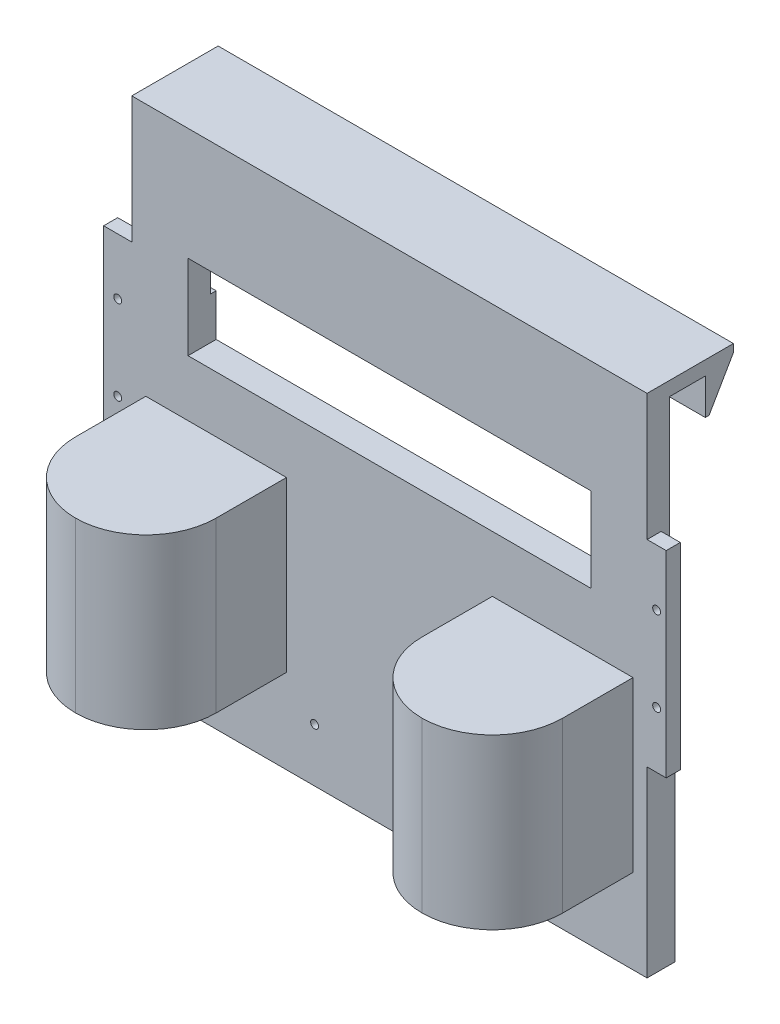
SolidWorks part; units mm, degrees
ref_plane "Alzado" through (0, 0, 0) normal (0, 0, 1) x (1, 0, 0)
ref_plane "Planta" through (0, 0, 0) normal (0, 1, 0) x (1, 0, 0)
ref_plane "Vista lateral" through (0, 0, 0) normal (1, 0, 0) x (0, 0, -1)
sketch "Croquis1" plane through (0, 0, 0) normal (0, 0, 1) x (1, 0, 0)
  line L1 (0, 0) -> (180, 0)
  line L2 (0, 0) -> (0, 180)
  line L3 (0, 180) -> (180, 180)
  line L4 (180, 0) -> (180, 180)
  dimension "D1" = 180
extrude "Saliente-Extruir1" add sketch "Croquis1" along normal blind 30.7
sketch "Croquis2" plane through (0, 0, 0) normal (0, 0, -1) x (-1, 0, 0)
  line L0 (-180, 0) -> (-180, 180) construction
  line L1 (-180, 162.21) -> (0, 162.21)
  line L2 (-180, 162.21) -> (-180, 0)
  line L3 (-180, 0) -> (0, 0)
  line L4 (0, 162.21) -> (0, 0)
  line L5 (-180, 180) -> (0, 180) construction
  dimension "D1" = 17.79
extrude "Cortar-Extruir1" cut sketch "Croquis2" against normal blind 20.7
sketch "Croquis3" plane through (0, 0, 0) normal (-1, 0, 0) x (0, 0, 1)
  line L0 (30.7, 180) -> (0, 180) construction
  line L1 (20.7, 162.21) -> (10, 162.21)
  line L2 (20.7, 162.21) -> (20.7, 175)
  line L3 (20.7, 175) -> (10, 175)
  line L4 (10, 162.21) -> (10, 175)
  dimension "D1" = 5
  dimension "D2" = 10.7
extrude "Cortar-Extruir2" cut sketch "Croquis3" against normal blind 274.7
sketch "Croquis4" plane through (180, 0, 0) normal (1, 0, 0) x (0, 0, -1)
  line L8 (-20.7, 0) -> (-20.7, 175)
  line L9 (-20.7, 175) -> (-10, 175)
  line L10 (-10, 175) -> (-10, 162.21)
  line L11 (-10, 162.21) -> (0, 162.21)
  line L12 (0, 162.21) -> (0, 180)
  line L13 (0, 180) -> (-30.7, 180)
  line L14 (-30.7, 180) -> (-30.7, 0)
  line L15 (-30.7, 0) -> (-20.7, 0)
  line L16 (-20.7, 0) -> (-20.7, 175)
  line L17 (-20.7, 175) -> (-10, 175)
  line L18 (-10, 175) -> (-10, 162.21)
  line L19 (-10, 162.21) -> (0, 162.21)
  line L20 (0, 162.21) -> (0, 180)
  line L21 (0, 180) -> (-30.7, 180)
  line L22 (-30.7, 180) -> (-30.7, 0)
  line L23 (-30.7, 0) -> (-20.7, 0)
  dimension "D1" = 0
extrude "Saliente-Extruir2" add sketch "Croquis4" along normal blind 20
sketch "Croquis5" plane through (0, 0, 20.7) normal (0, 0, -1) x (-1, 0, 0)
  line L0 (-10, 125) -> (-10, 0) construction
  line L1 (-55, 38) -> (-10, 38)
  line L2 (-55, 38) -> (-55, 0)
  line L3 (-55, 0) -> (0, 0)
  line L4 (0, 38) -> (0, 0)
  line L5 (-148.2, 38) -> (-193.2, 38)
  line L6 (-148.2, 38) -> (-148.2, 0)
  line L7 (-148.2, 0) -> (-200, 0)
  line L8 (-200, 38) -> (-200, 0)
  line L9 (0, 180) -> (-10, 180)
  line L10 (0, 180) -> (0, 135)
  line L11 (0, 135) -> (-10, 135)
  line L12 (-10, 180) -> (-10, 135)
  line L13 (-193.2, 0) -> (-193.2, 125) construction
  line L14 (-200, 180) -> (-193.2, 180)
  line L15 (-200, 180) -> (-200, 135)
  line L16 (-200, 135) -> (-193.2, 135)
  line L17 (-193.2, 180) -> (-193.2, 135)
  line L20 (-200, 38) -> (-200, 65)
  line L21 (-200, 65) -> (-193.2, 65)
  line L22 (-193.2, 38) -> (-193.2, 65)
  line L24 (0, 38) -> (0, 65)
  line L25 (0, 65) -> (-10, 65)
  line L26 (-10, 38) -> (-10, 65)
  dimension "D1" = 65
  dimension "D2" = 65
  dimension "D3" = 45
  dimension "D4" = 45
extrude "Cortar-Extruir3" cut sketch "Croquis5" along normal blind 147 and the other way blind 147
sketch "Croquis6" plane through (0, 0, 20.7) normal (0, 0, -1) x (-1, 0, 0)
  line L1 (-55, 0) -> (-148.2, 0)
  line L2 (-55, 0) -> (-55, 38)
  line L3 (-55, 38) -> (-148.2, 38)
  line L4 (-148.2, 0) -> (-148.2, 38)
  line L5 (-193.2, 65) -> (-200, 65)
  line L6 (-193.2, 65) -> (-193.2, 135)
  line L7 (-193.2, 135) -> (-200, 135)
  line L8 (-200, 65) -> (-200, 135)
  line L9 (0, 135) -> (-10, 135)
  line L10 (0, 135) -> (0, 65)
  line L11 (0, 65) -> (-10, 65)
  line L12 (-10, 135) -> (-10, 65)
extrude "Cortar-Extruir4" cut sketch "Croquis6" against normal blind 5
sketch "Croquis7" plane through (0, 0, 20.7) normal (0, 0, -1) x (-1, 0, 0)
  line L0 (-10, 175) -> (-10, 38) construction
  line L1 (-193.2, 175) -> (-10, 175)
  line L2 (-193.2, 175) -> (-193.2, 125)
  line L3 (-193.2, 125) -> (-10, 125)
  line L4 (-10, 175) -> (-10, 125)
  dimension "D1" = 50
extrude "Cortar-Extruir5" cut sketch "Croquis7" against normal blind 2
sketch "Croquis8" plane through (0, 38, 0) normal (0, -1, 0) x (1, 0, 0)
  line L1 (55, 30.7) -> (10, 30.7)
  line L2 (55, 30.7) -> (55, 20.7)
  line L3 (55, 20.7) -> (10, 20.7)
  line L4 (10, 30.7) -> (10, 20.7)
  line L5 (148.2, 30.7) -> (193.2, 30.7)
  line L6 (148.2, 30.7) -> (148.2, 20.7)
  line L7 (148.2, 20.7) -> (193.2, 20.7)
  line L8 (193.2, 30.7) -> (193.2, 20.7)
extrude "Saliente-Extruir3" add sketch "Croquis8" along normal up to surface (38 mm away) up to face at (101.6, 0, 28.2)
sketch "Croquis9" plane through (0, 0, 30.7) normal (0, 0, 1) x (1, 0, 0)
  line L0 (193.2, 180) -> (10, 180) construction
  line L1 (30, 140) -> (173.2, 140)
  line L2 (30, 140) -> (30, 110)
  line L3 (30, 110) -> (173.2, 110)
  line L4 (173.2, 140) -> (173.2, 110)
  line L5 (193.2, 135) -> (193.2, 180) construction
  line L6 (10, 180) -> (10, 135) construction
  line L7 (148.2, 0) -> (148.2, 38) construction
  line L8 (55, 0) -> (55, 38) construction
  line L10 (200, 65) -> (193.2, 65) construction
  line L11 (0, 135) -> (10, 135) construction
  line L12 (10, 65) -> (0, 65) construction
  line L13 (193.2, 135) -> (200, 135) construction
  circle A0 centre (5, 115) radius 1.4
  circle A1 centre (5, 85) radius 1.4
  circle A2 centre (196.6, 115) radius 1.4
  circle A3 centre (196.6, 85) radius 1.4
  circle A4 centre (128.2, 19) radius 1.4
  circle A5 centre (75, 19) radius 1.4
  point P26 (0, 0)
  point P27 (55, 19)
  point P28 (0, 0)
  point P31 (196.6, 65)
  point P32 (0, 0)
  point P35 (5, 135)
  dimension "D7" = 2.8
  dimension "D1" = 30
  dimension "D2" = 40
  dimension "D3" = 20
  dimension "D4" = 20
  dimension "D5" = 20
  dimension "D6" = 20
  dimension "D8" = 20
  dimension "D9" = 20
  dimension "D10" = 20
  dimension "D11" = 20
extrude "Cortar-Extruir6" cut sketch "Croquis9" against normal blind 20
chamfer "Chaflán1" distance 15 angle 30 1 edges at (101.6, 162.21, 0) first distance on face at (101.6, 171.105, 0)
sketch "Croquis10" plane through (0, 0, 30.7) normal (0, 0, 1) x (1, 0, 0)
  line L0 (10, 0) -> (193.2, 0) construction
  line L1 (138.2, 90) -> (188.2, 90)
  line L2 (138.2, 90) -> (138.2, 30)
  line L3 (138.2, 30) -> (188.2, 30)
  line L4 (188.2, 90) -> (188.2, 30)
  line L5 (15, 90) -> (65, 90)
  line L6 (15, 90) -> (15, 30)
  line L7 (15, 30) -> (65, 30)
  line L8 (65, 90) -> (65, 30)
  line L9 (193.2, 0) -> (193.2, 65) construction
  line L10 (10, 65) -> (10, 0) construction
  dimension "D1" = 50
  dimension "D2" = 5
  dimension "D3" = 60
  dimension "D4" = 30
  dimension "D5" = 5
extrude "Saliente-Extruir4" add sketch "Croquis10" along normal blind 50
fillet "Redondeo1" radius 25 4 edges at (15, 60, 80.7) (65, 60, 80.7) (138.2, 60, 80.7) (188.2, 60, 80.7)
sketch "Croquis11" plane through (0, 30, 0) normal (0, -1, 0) x (1, 0, 0)
  circle A0 centre (163.2, 55.7) radius 10.8
  circle A1 centre (40, 55.7) radius 10.8
  dimension "D1" = 21.6
  dimension "D2" = 21.6
extrude "Cortar-Extruir7" cut sketch "Croquis11" against normal blind 40
